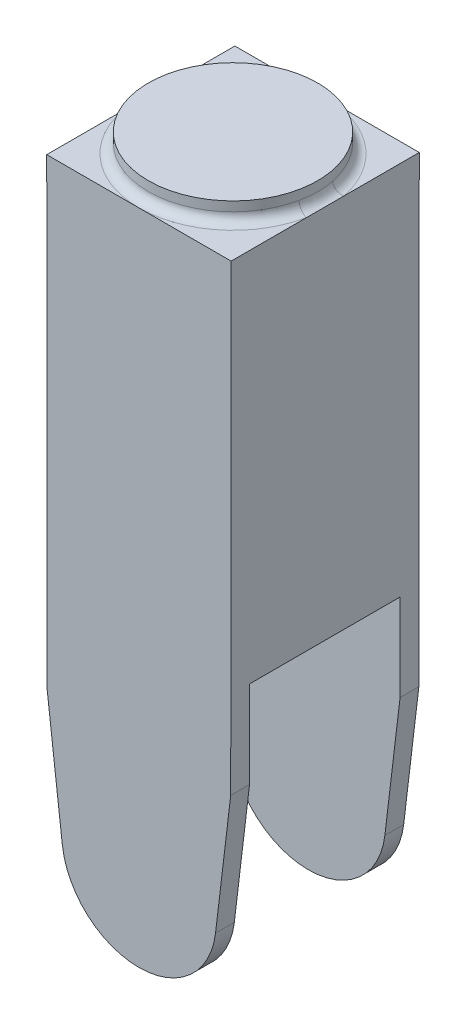
SolidWorks part; units mm, degrees
ref_plane "Front Plane" through (0, 0, 0) normal (0, 0, 1) x (1, 0, 0)
ref_plane "Top Plane" through (0, 0, 0) normal (0, 1, 0) x (1, 0, 0)
ref_plane "Right Plane" through (0, 0, 0) normal (1, 0, 0) x (0, 0, -1)
sketch "Sketch1" plane through (0, 0, 0) normal (0, 0, 1) x (1, 0, 0)
  line L0 (-49, 0) -> (49, 0)
  line L1 (49, 0) -> (48.785, -245.9999)
  line L2 (48.785, -245.9999) -> (40.7099, -313.5187)
  line L3 (0, -30.496) -> (0, -367.1548) construction
  line L4 (-48.785, -245.9999) -> (-40.7099, -313.5187)
  line L5 (-49, 0) -> (-48.785, -245.9999)
  arc A0 (-40.7099, -313.5187) -> (40.7099, -313.5187) centre (0, -308.6499) ccw
  point P15 (0, 0)
  dimension "D3" = 82
  dimension "D6" = 173.23
  dimension "D1" = 49
  dimension "D2" = 246
  dimension "D5" = 68
extrude "Boss-Extrude1" add sketch "Sketch1" along normal blind 50 and the other way blind 50 contours L5 L4 A0 L2 L1 L0
sketch "Sketch2" plane through (49, -0.0428, 0) normal (1, -0.0009, 0) x (0, 0, -1)
  line L0 (-50, -349.6498) -> (50, -349.6498) construction
  line L1 (40, -199.6498) -> (-40, -199.6498)
  line L2 (40, -199.6498) -> (40, -349.6498)
  line L3 (40, -349.6498) -> (-40, -349.6498)
  line L4 (-40, -199.6498) -> (-40, -349.6498)
  line L5 (0, -349.6498) -> (0, -199.6498) construction
  line L6 (40, -274.6498) -> (-40, -274.6498) construction
  point P0 (0, -274.6498)
  dimension "D1" = 150
  dimension "D2" = 80
  dimension "D3" = 0
extrude "Cut-Extrude1" cut sketch "Sketch2" against normal through all
sketch "Sketch3" plane through (0, 0, 0) normal (0, 1, 0) x (1, 0, 0)
  circle A0 centre (0, 0) radius 45
  dimension "D1" = 90
extrude "Boss-Extrude2" add sketch "Sketch3" along normal blind 10
fillet "Fillet1" radius 5 1 edges at (0, 0, 45)
sketch "Sketch4" plane through (0, 0, 0) normal (0, 0, 1) x (1, 0, 0)
  point P0 (0, -308.6499)
move or copy body "Body-Move/Copy1" bodies to move or copy 103 copy no translate (0, 308.6499, 0)
